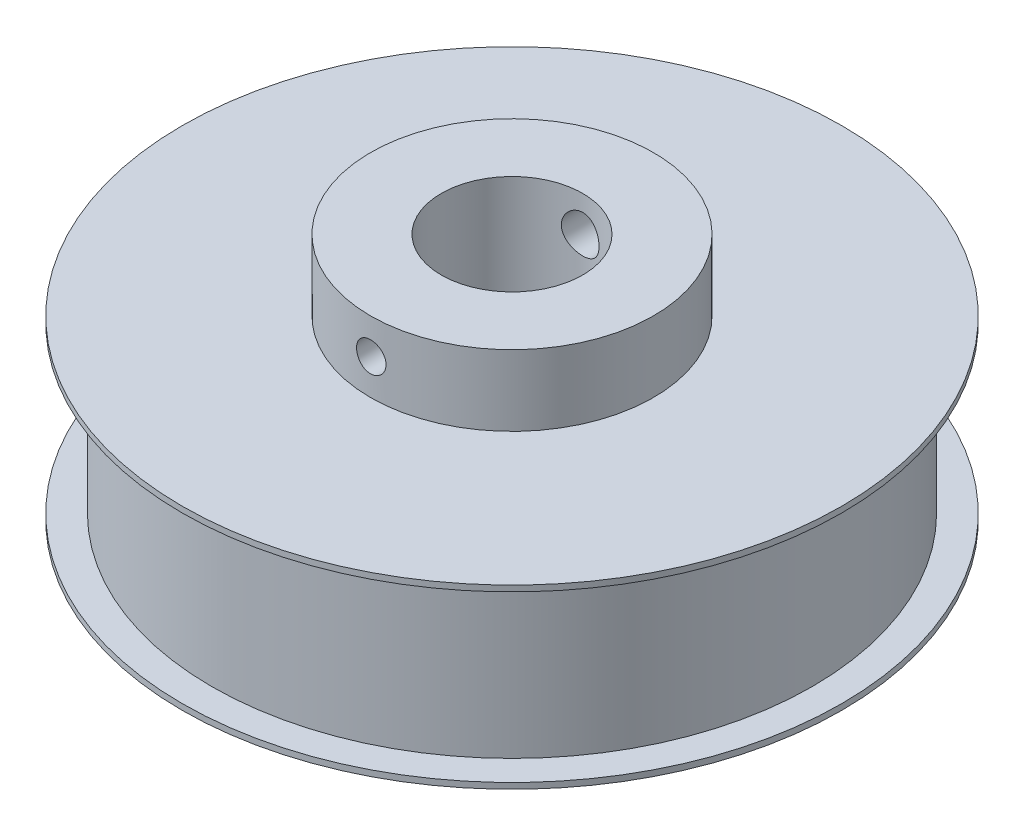
SolidWorks part; units mm, degrees
ref_plane "Alzado" through (0, 0, 0) normal (1, 0, 0) x (0, 1, 0)
ref_plane "Planta" through (0, 0, 0) normal (0, 0, 1) x (0, 1, 0)
ref_plane "Vista lateral" through (0, 0, 0) normal (0, 1, 0) x (-1, 0, 0)
sketch "Croquis1" plane through (0, 0, 0) normal (0, 1, 0) x (-1, 0, 0)
  circle A0 centre (0, 0) radius 25.465
  dimension "D1" = 50.93
extrude "Saliente-Extruir1" add sketch "Croquis1" along normal mid plane 15
sketch "Croquis2" plane through (0, 7.5, 0) normal (0, 1, 0) x (-1, 0, 0)
  circle A3 centre (0, 0) radius 27.965
  dimension "D1" = 55.93
extrude "Saliente-Extruir2" add sketch "Croquis2" against normal blind 0.5
extrude "Saliente-Extruir3" add sketch "Croquis2<2>" along normal blind 0.5 from surface starting at face at (0, -7.5, 25.465)
sketch "Croquis2<2>" plane through (0, 7.5, 0) normal (0, 1, 0) x (-1, 0, 0) same geometry as "Croquis2"
sketch "Croquis3" plane through (0, -7.5, 0) normal (0, 1, 0) x (-1, 0, 0)
  circle A0 centre (0, 0) radius 19
  dimension "D1" = 38
extrude "Saliente-Extruir4" add sketch "Croquis3" along normal blind 21
sketch "Croquis4" plane through (0, -7, 0) normal (0, 1, 0) x (-1, 0, 0)
  circle A0 centre (0, 0) radius 6
  dimension "D1" = 12
extrude "Cortar-Extruir1" cut sketch "Croquis4" against normal through all both and the other way through all
sketch "Croquis5" plane through (0, 13.5, 0) normal (0, 1, 0) x (-1, 0, 0)
  circle A0 centre (0, 0) radius 12
  circle A2 centre (0, 0) radius 19 construction
  circle A3 centre (0, 0) radius 19
  dimension "D1" = 24
extrude "Cortar-Extruir2" cut sketch "Croquis5" against normal up to surface (6 mm away) up to face at (0, 7.5, 19)
ref_plane "Plano1" through (0, 0, 12) normal (0, 0, 1) x (1, 0, 0)
sketch "Croquis6" plane through (-12, 0, 12) normal (0, 0, -1) x (0, 1, 0)
  line L0 (13.5, 24) -> (7.5, 24) construction
  line L1 (7.5, -15.965) -> (7.5, 39.965) construction
  line L2 (13.5, 24) -> (7.5, 24) construction
  line L3 (10.5, 24) -> (10.5, 0) construction
  line L4 (7.5, 0) -> (13.5, 0) construction
  point P11 (10.5, 12)
hole_wizard "Taladro roscado M31" positions "Croquis6" profile "Croquis7" tap size "M3" standard "DIN" end condition up to next
sketch "Croquis7" plane through (0, 10.5, 12) normal (1, 0, 0) x (0, -1, 0)
  line L0 (0, 0) -> (0, 6)
  line L1 (0, 6) -> (1.25, 6)
  line L2 (1.25, 6) -> (1.25, 0)
  line L5 (1.25, 0) -> (0, 0)
  line L11 (0, -6.35) -> (0, 107.95) construction
  dimension "Diámetro de perforador para roscar hasta el siguiente" = 2.5
  dimension "Profundidad de perforador para roscar hasta el siguiente" = 6
cosmetic thread "Rosca de taladro1" parameters "D2"=3
ref_plane "Plano2" through (0, 0, 0) normal (0, 0, 1) x (1, 0, 0)
sketch "Croquis8" [suppressed] plane through (0, 0, 0) normal (0, 0, 1) x (1, 0, 0)
  circle A0 centre (0, 10.5) radius 1.25 construction
  circle A1 centre (0, 10.5) radius 1.25
ref_axis "Eje2" [suppressed] through (0, 10.5, -21.2911) along (0, 0, 1)
ref_plane "Plano3" [suppressed] through (0, 12, 0) normal (0, -1, 0) x (-1, 0, 0)
sketch "Croquis9" plane through (0, 12, 0) normal (0, 0, 1) x (-1, 0, 0)
  circle A0 centre (0, 1.5) radius 1.25 construction
  circle A1 centre (0, 1.5) radius 1.25 construction
  point P4 (0, 1.5)
hole_wizard "Taladro de margen para M32" positions "Croquis9" profile "Croquis10" hole size "M3" standard "Ansi Metric" end condition up to next
sketch "Croquis10" plane through (0, 10.5, 0) normal (1, 0, 0) x (0, -1, 0)
  line L0 (0, 0) -> (0, 12)
  line L1 (0, 12) -> (1.6, 12)
  line L2 (1.6, 12) -> (1.6, 0)
  line L5 (1.6, 0) -> (0, 0)
  line L11 (0, -6.35) -> (0, 107.95) construction
  dimension "Diámetro de taladro hasta el siguiente" = 3.2
  dimension "Profundidad de taladro hasta el siguiente" = 12
equation "\"Dp\"= 50.93"
equation "\"D1@Croquis1\"=\"Dp\""
equation "\"Dm\"= 38"
equation "\"De\"= \"Dp\" + 5"
equation "\"F\"= 15"
equation "\"L\"= 21"
equation "\"D1@Croquis2\"=\"De\""
equation "\"D1@Saliente-Extruir1\"=\"F\""
equation "\"D1@Saliente-Extruir4\"=\"L\""
equation "\"deje\"=12"
equation "\"D1@Croquis4\"=\"deje\""
equation "\"D1@Croquis3\"=\"Dm\""
